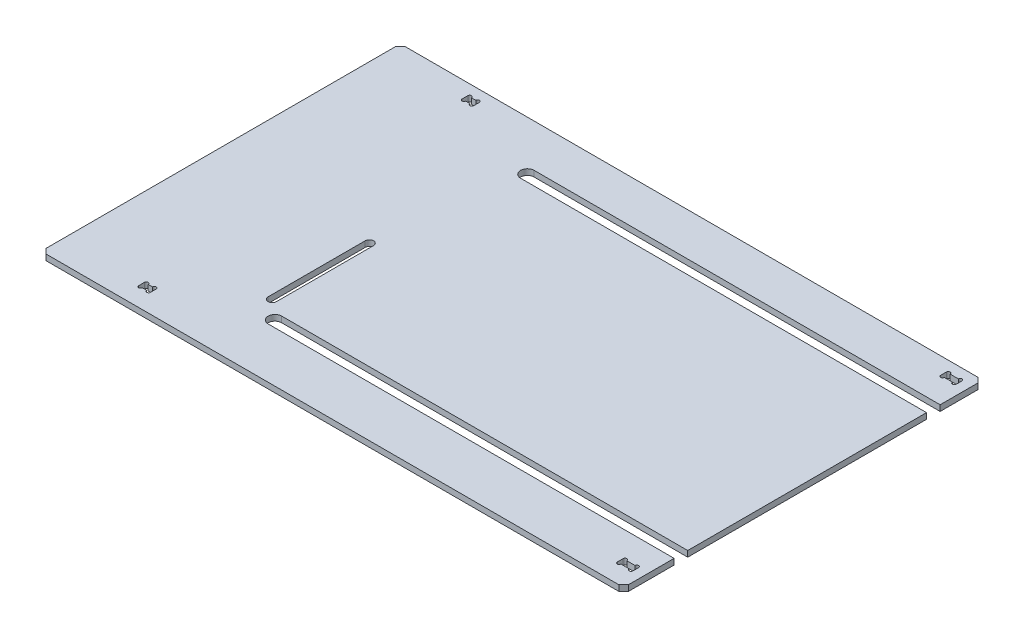
SolidWorks part; units mm, degrees
ref_plane "정면" through (0, 0, 0) normal (0, 0, 1) x (1, 0, 0)
ref_plane "윗면" through (0, 0, 0) normal (0, 1, 0) x (1, 0, 0)
ref_plane "우측면" through (0, 0, 0) normal (1, 0, 0) x (0, 0, -1)
sketch "스케치1" plane through (0, 0, 0) normal (0, 1, 0) x (1, 0, 0)
  line L1 (0, 0) -> (300, 0)
  line L2 (0, 0) -> (0, 185)
  line L3 (0, 185) -> (300, 185)
  line L4 (300, 0) -> (300, 185)
  dimension "D1" = 185
  dimension "D2" = 300
extrude "보스-돌출1" add sketch "스케치1" along normal blind 3
sketch "스케치2" plane through (0, 3, 0) normal (0, 1, 0) x (1, 0, 0)
  line L0 (92.9, 63.1066) -> (93.0904, 63.1066) construction
  line L1 (92.9, 60.6066) -> (92.9, 65.6066) construction
  line L3 (78.8, 63.1066) -> (78.8, 88.1066)
  line L4 (78.8, 38.1066) -> (83.1, 38.1066)
  line L5 (78.8, 38.1066) -> (78.8, 63.1066)
  line L6 (78.8, 88.1066) -> (83.1, 88.1066)
  line L7 (83.1, 38.1066) -> (83.1, 88.1066)
  line L8 (80, 83.2292) -> (80, 85.4866) construction
  line L10 (80.9, 83.2292) -> (80.9, 85.4866) construction
  dimension "D1" = 1.2
  dimension "D2" = 2.2
  dimension "D3" = 25
  dimension "D4" = 25
extrude "컷-돌출1" cut sketch "스케치2" against normal blind 10
sketch "스케치3" plane through (0, 3, 0) normal (0, 1, 0) x (1, 0, 0)
  line L0 (83.1, 88.1066) -> (78.8, 88.1066) construction
  line L1 (78.8, 38.1066) -> (83.1, 38.1066) construction
  circle A0 centre (80.95, 88.1066) radius 2.15
  circle A1 centre (80.95, 38.1066) radius 2.15
extrude "컷-돌출2" cut sketch "스케치3" against normal blind 10
sketch "스케치4" plane through (0, 3, 0) normal (0, 1, 0) x (1, 0, 0)
  line L0 (164.1565, 162) -> (181.0168, 162) construction
  line L1 (300, 163) -> (90.9, 163)
  line L2 (300, 163) -> (300, 156)
  line L3 (300, 156) -> (90.9, 156)
  line L4 (90.9, 163) -> (90.9, 156)
  line L5 (90.9, 26) -> (300, 26)
  line L6 (90.9, 26) -> (90.9, 33)
  line L7 (90.9, 33) -> (300, 33)
  line L8 (300, 26) -> (300, 33)
  line L9 (164.1565, 157) -> (181.0168, 157) construction
  line L10 (164.1565, 32) -> (181.0168, 32) construction
  line L13 (300, 0) -> (300, 185) construction
  dimension "D1" = 1
  dimension "D2" = 1
  dimension "D3" = 1
  dimension "D4" = 10
extrude "컷-돌출3" cut sketch "스케치4" against normal blind 10
sketch "스케치5" plane through (0, 3, 0) normal (0, 1, 0) x (1, 0, 0)
  line L0 (90.9, 163) -> (90.9, 156) construction
  line L3 (90.9, 33) -> (90.9, 26) construction
  circle A0 centre (90.9, 159.5) radius 3.5
  circle A3 centre (90.9, 29.5) radius 3.5
extrude "컷-돌출5" cut sketch "스케치5" against normal blind 10
chamfer "모따기1" distance 2.5 angle 45 4 edges at (0, 1.5, 0) (0, 1.5, -185) (300, 1.5, 0) (300, 1.5, -185)
sketch "스케치6" plane through (0, 0, 0) normal (0, -1, 0) x (1, 0, 0)
  line L0 (295, -179.5) -> (295, -9.5) construction
  line L1 (46.5, -179.25) -> (40.5, -179.25)
  line L2 (46.5, -179.25) -> (46.5, -176.25)
  line L3 (46.5, -176.25) -> (40.5, -176.25)
  line L4 (40.5, -179.25) -> (40.5, -176.25)
  line L5 (287, -176.25) -> (295, -176.25)
  line L6 (287, -176.25) -> (287, -179.25)
  line L7 (287, -179.25) -> (295, -179.25)
  line L8 (295, -176.25) -> (295, -179.25)
  line L9 (300, -94.5) -> (244.3606, -94.5) construction
  line L10 (300, -33) -> (300, -156) construction
  line L11 (295, -12.75) -> (295, -9.75)
  line L12 (287, -9.75) -> (295, -9.75)
  line L13 (287, -12.75) -> (287, -9.75)
  line L14 (287, -12.75) -> (295, -12.75)
  line L15 (40.5, -9.75) -> (40.5, -12.75)
  line L16 (46.5, -12.75) -> (40.5, -12.75)
  line L17 (46.5, -9.75) -> (46.5, -12.75)
  line L18 (46.5, -9.75) -> (40.5, -9.75)
  dimension "D1" = 6
  dimension "D2" = 3
  dimension "D3" = 3
extrude "컷-돌출6" cut sketch "스케치6" against normal blind 3
sketch "스케치7" plane through (0, 3, 0) normal (0, 1, 0) x (1, 0, 0)
  line L0 (40.5, 12.75) -> (46.5, 12.75) construction
  line L1 (46.5, 9.75) -> (40.5, 9.75) construction
  line L2 (295, 9.75) -> (287, 9.75) construction
  line L3 (287, 12.75) -> (295, 12.75) construction
  line L4 (23.5484, 94.5) -> (300, 94.5) construction
  line L7 (300, 33) -> (300, 156) construction
  circle A0 centre (41.4422, 12.75) radius 0.9422
  circle A1 centre (45.5578, 12.75) radius 0.9422
  circle A2 centre (45.5578, 9.75) radius 0.9422
  circle A3 centre (41.4422, 9.75) radius 0.9422
  circle A4 centre (294.0578, 9.75) radius 0.9422
  circle A5 centre (294.0578, 12.75) radius 0.9422
  circle A6 centre (287.9422, 12.75) radius 0.9422
  circle A7 centre (287.9422, 9.75) radius 0.9422
  circle A8 centre (287.9422, 179.25) radius 0.9422
  circle A9 centre (287.9422, 176.25) radius 0.9422
  circle A10 centre (294.0578, 176.25) radius 0.9422
  circle A11 centre (294.0578, 179.25) radius 0.9422
  circle A12 centre (41.4422, 179.25) radius 0.9422
  circle A13 centre (45.5578, 179.25) radius 0.9422
  circle A14 centre (45.5578, 176.25) radius 0.9422
  circle A15 centre (41.4422, 176.25) radius 0.9422
  point P36 (300, 94.5)
extrude "컷-돌출7" cut sketch "스케치7" against normal blind 10
